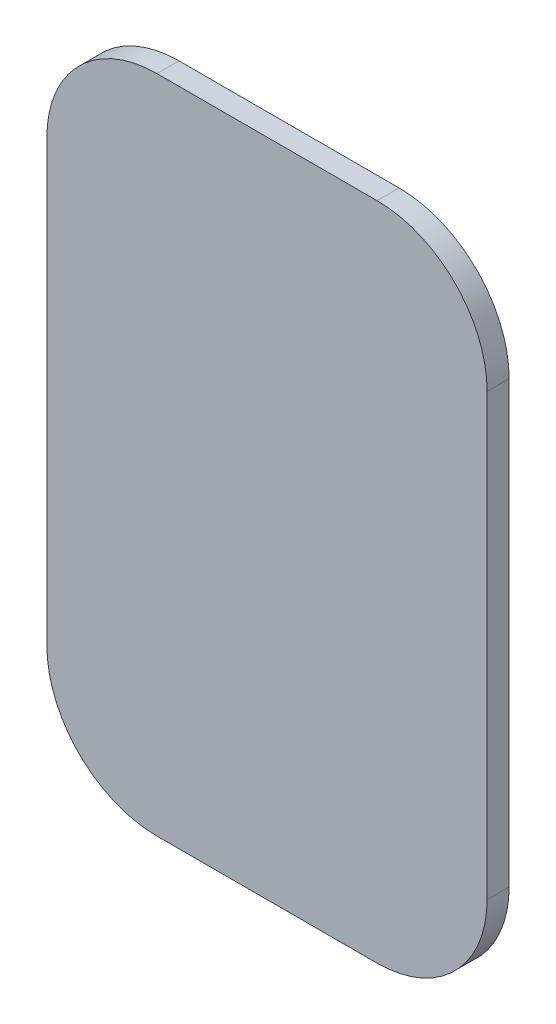
SolidWorks part; units mm, degrees
ref_plane "Front Plane" through (0, 0, 0) normal (0, 0, 1) x (1, 0, 0)
ref_plane "Top Plane" through (0, 0, 0) normal (0, 1, 0) x (1, 0, 0)
ref_plane "Right Plane" through (0, 0, 0) normal (1, 0, 0) x (0, 0, -1)
sketch "Sketch1" plane through (0, 0, 0) normal (0, 0, 1) x (1, 0, 0)
  line L0 (26.4839, -25.2645) -> (26.4839, 25.5355)
  line L1 (13.7839, 38.2355) -> (-11.6161, 38.2355)
  line L2 (-24.3161, 25.5355) -> (-24.3161, -25.2645)
  line L3 (-11.6161, -37.9645) -> (13.7839, -37.9645)
  arc A0 (13.7839, -37.9645) -> (26.4839, -25.2645) centre (13.7839, -25.2645) ccw
  arc A1 (26.4839, 25.5355) -> (13.7839, 38.2355) centre (13.7839, 25.5355) ccw
  arc A2 (-11.6161, 38.2355) -> (-24.3161, 25.5355) centre (-11.6161, 25.5355) ccw
  arc A3 (-24.3161, -25.2645) -> (-11.6161, -37.9645) centre (-11.6161, -25.2645) ccw
  dimension "D1" = 50.8
base flange "Base-Flange1" sketch "Sketch1" thickness 2.54 reverse thickness direction no parameters "D1"=0.7366
sketch "Bend-Lines1" [suppressed] plane through (0, 0, 0) normal (0, 1, 0) x (1, 0, 0)
sketch "Bounding-Box1" [suppressed] plane through (0, 0, 0) normal (0, 1, 0) x (1, 0, 0)
sheet metal parameters "Sheet-Metal1" thickness 2.54 parameters "D1"=0.7366
flat pattern "Flat-Pattern1" [suppressed]
sketch "Bend-Lines2" plane through (0, 0, 0) normal (0, 1, 0) x (1, 0, 0)
sketch3d "Bounding-Box2" [suppressed]
  line L0 (-12.7, -12.7, 0) -> (-12.7, 63.5, 0) construction
  line L1 (38.1, -12.7, 0) -> (38.1, 63.5, 0) construction
  line L2 (-12.7, -12.7, 0) -> (38.1, -12.7, 0) construction
  line L3 (-12.7, 63.5, 0) -> (38.1, 63.5, 0) construction
